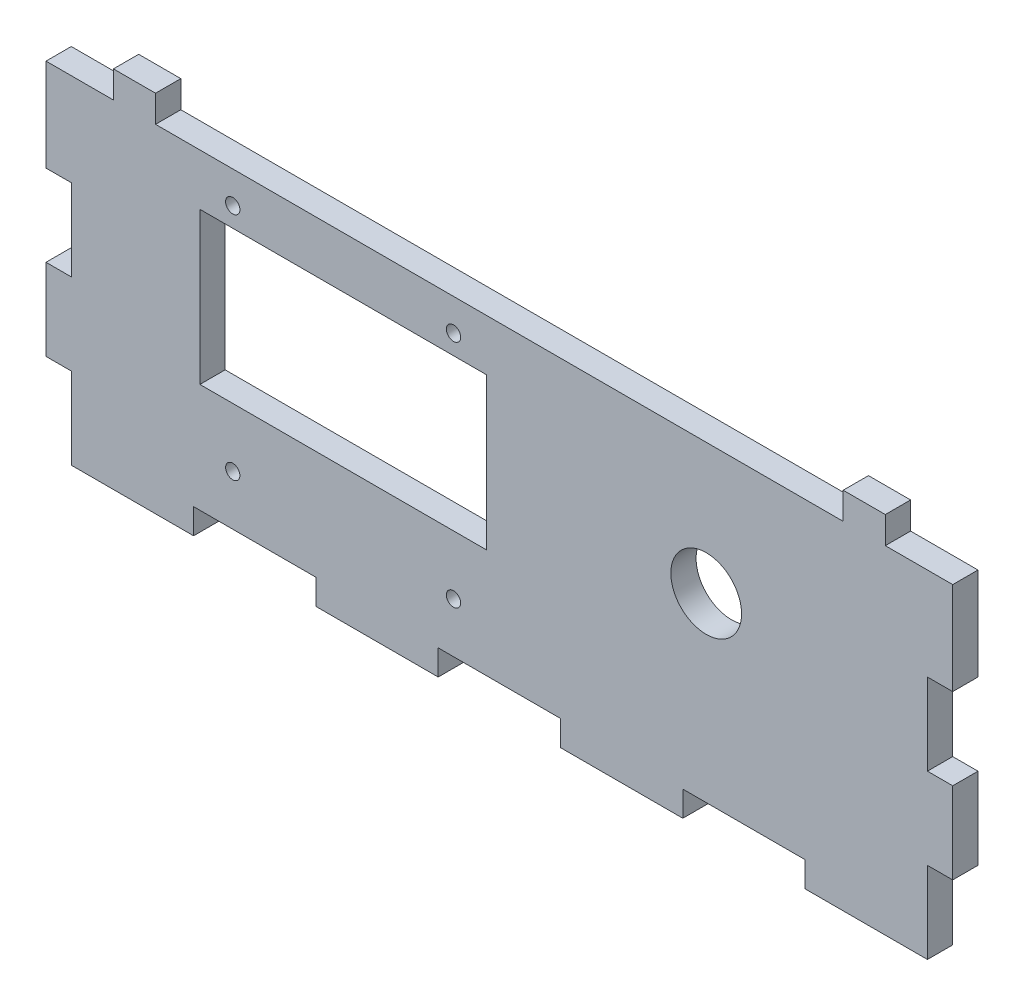
SolidWorks part; units mm, degrees
ref_plane "Alzado" through (0, 0, 0) normal (0, 0, 1) x (1, 0, 0)
ref_plane "Planta" through (0, 0, 0) normal (0, 1, 0) x (1, 0, 0)
ref_plane "Vista lateral" through (0, 0, 0) normal (1, 0, 0) x (0, 0, -1)
sketch "Croquis1" plane through (0, 0, 0) normal (0, 0, 1) x (1, 0, 0)
  line L0 (0, -17.0016) -> (0, -14.0016)
  line L1 (-48.39, -14.0016) -> (0, -14.0016) construction
  line L2 (0, -17.0016) -> (104.61, -17.0016)
  line L3 (101.61, -17.0016) -> (101.61, -49.332) construction
  line L4 (-227.956, -78.0016) -> (93.758, -78.0016) construction
  line L5 (-48.39, -14.0016) -> (-48.39, -78.0016) construction
  line L6 (78.6222, -39.0016) -> (-38.712, -39.0016) construction
  line L7 (0, -14.0016) -> (0, -17.0016) construction
  line L8 (0, -17.0016) -> (-48.39, -17.0016) construction
  line L9 (-48.39, -14.0016) -> (-38.712, -14.0016)
  line L10 (-38.712, -14.0016) -> (-38.712, -17.0016)
  line L11 (-38.712, -17.0016) -> (-29.034, -17.0016)
  line L12 (-29.034, -17.0016) -> (-29.034, -14.0016)
  line L13 (-29.034, -14.0016) -> (-19.356, -14.0016)
  line L14 (-19.356, -14.0016) -> (-19.356, -17.0016)
  line L15 (-19.356, -17.0016) -> (-9.678, -17.0016)
  line L16 (-9.678, -17.0016) -> (-9.678, -14.0016)
  line L17 (-9.678, -14.0016) -> (0, -14.0016)
  line L18 (104.61, -17.0016) -> (104.61, -78.0016) construction
  line L19 (104.61, -17.0016) -> (104.61, -29.2016)
  line L20 (104.61, -29.2016) -> (101.61, -29.2016)
  line L21 (101.61, -29.2016) -> (101.61, -41.4016)
  line L22 (101.61, -41.4016) -> (104.61, -41.4016)
  line L23 (104.61, -41.4016) -> (104.61, -53.6016)
  line L24 (104.61, -53.6016) -> (101.61, -53.6016)
  line L25 (101.61, -53.6016) -> (101.61, -65.8016)
  line L26 (101.61, -65.8016) -> (104.61, -65.8016)
  line L27 (104.61, -65.8016) -> (104.61, -78.0016)
  line L28 (-45.39, -56.5563) -> (-45.39, 45.6638) construction
  line L29 (-48.39, -14.0016) -> (-48.39, -26.8016)
  line L30 (-48.39, -26.8016) -> (-45.39, -26.8016)
  line L31 (-45.39, -26.8016) -> (-45.39, -39.6016)
  line L32 (-45.39, -39.6016) -> (-48.39, -39.6016)
  line L33 (-48.39, -39.6016) -> (-48.39, -52.4016)
  line L34 (-48.39, -52.4016) -> (-45.39, -52.4016)
  line L35 (-45.39, -52.4016) -> (-45.39, -65.2016)
  line L36 (-45.39, -65.2016) -> (-48.39, -65.2016)
  line L37 (-48.39, -65.2016) -> (-48.39, -78.0016)
  line L38 (-102.5031, -75.0016) -> (75.9308, -75.0016) construction
  line L39 (-124.386, -156.1001) -> (179.1879, -156.1001) construction
  line L40 (-48.39, -153.1001) -> (104.61, -153.1001) construction
  line L41 (-48.39, -78.0016) -> (-34.4809, -78.0016)
  line L42 (-34.4809, -78.0016) -> (-34.4809, -75.0016)
  line L43 (-34.4809, -75.0016) -> (-20.5718, -75.0016)
  line L44 (-20.5718, -75.0016) -> (-20.5718, -78.0016)
  line L45 (-20.5718, -78.0016) -> (-6.6627, -78.0016)
  line L46 (-6.6627, -78.0016) -> (-6.6627, -75.0016)
  line L47 (-6.6627, -75.0016) -> (7.2464, -75.0016)
  line L48 (7.2464, -75.0016) -> (7.2464, -78.0016)
  line L49 (7.2464, -78.0016) -> (21.1555, -78.0016)
  line L50 (21.1555, -78.0016) -> (21.1555, -75.0016)
  line L51 (21.1555, -75.0016) -> (35.0645, -75.0016)
  line L52 (35.0645, -75.0016) -> (35.0645, -78.0016)
  line L53 (35.0645, -78.0016) -> (48.9736, -78.0016)
  line L54 (48.9736, -78.0016) -> (48.9736, -75.0016)
  line L55 (48.9736, -75.0016) -> (62.8827, -75.0016)
  line L56 (62.8827, -75.0016) -> (62.8827, -78.0016)
  line L57 (62.8827, -78.0016) -> (76.7918, -78.0016)
  line L58 (76.7918, -78.0016) -> (76.7918, -75.0016)
  line L59 (76.7918, -75.0016) -> (90.7009, -75.0016)
  line L60 (90.7009, -75.0016) -> (90.7009, -78.0016)
  line L61 (90.7009, -78.0016) -> (104.61, -78.0016)
  line L62 (-48.39, -153.1001) -> (-48.39, -260.7101) construction
  line L63 (-48.39, -260.7101) -> (104.61, -260.7101) construction
  line L64 (104.61, -153.1001) -> (104.61, -260.7101) construction
  line L65 (-68.7634, -257.7101) -> (144.8732, -257.7101) construction
  line L66 (101.61, -78.0016) -> (101.61, -269.1968) construction
  line L67 (-45.39, -153.1001) -> (-45.39, -251.8965) construction
  line L68 (-34.4809, -78.0016) -> (-34.4809, -243.0877) construction
  line L69 (-20.5718, -78.0016) -> (-20.5718, -243.0877) construction
  line L70 (-6.6627, -75.0016) -> (-6.6627, -243.0877) construction
  line L71 (7.2464, -75.0016) -> (7.2464, -243.0877) construction
  line L72 (21.1555, -75.0016) -> (21.1555, -243.0877) construction
  line L73 (35.0645, -75.0016) -> (35.0645, -243.0877) construction
  line L74 (48.9736, -75.0016) -> (48.9736, -243.0877) construction
  line L75 (62.8827, -75.0016) -> (62.8827, -243.0877) construction
  line L76 (76.7918, -75.0016) -> (76.7918, -243.0877) construction
  line L77 (90.7009, -75.0016) -> (90.7009, -243.0877) construction
  line L78 (-34.4809, -156.1001) -> (-48.39, -156.1001)
  line L79 (-34.4809, -156.1001) -> (-34.4809, -153.1001)
  line L80 (-34.4809, -153.1001) -> (-20.5718, -153.1001)
  line L81 (-20.5718, -153.1001) -> (-20.5718, -156.1001)
  line L82 (-20.5718, -156.1001) -> (-6.6627, -156.1001)
  line L83 (-6.6627, -156.1001) -> (-6.6627, -153.1001)
  line L84 (-6.6627, -153.1001) -> (7.2464, -153.1001)
  line L85 (7.2464, -153.1001) -> (7.2464, -156.1001)
  line L86 (7.2464, -156.1001) -> (21.1555, -156.1001)
  line L87 (21.1555, -156.1001) -> (21.1555, -153.1001)
  line L88 (21.1555, -153.1001) -> (35.0645, -153.1001)
  line L89 (35.0645, -153.1001) -> (35.0645, -156.1001)
  line L90 (35.0645, -156.1001) -> (48.9736, -156.1001)
  line L91 (48.9736, -156.1001) -> (48.9736, -153.1001)
  line L92 (48.9736, -153.1001) -> (62.8827, -153.1001)
  line L93 (62.8827, -153.1001) -> (62.8827, -156.1001)
  line L94 (62.8827, -156.1001) -> (76.7918, -156.1001)
  line L95 (76.7918, -156.1001) -> (76.7918, -153.1001)
  line L96 (76.7918, -153.1001) -> (90.7009, -153.1001)
  line L97 (90.7009, -153.1001) -> (90.7009, -156.1001)
  line L98 (90.7009, -156.1001) -> (104.61, -156.1001)
  line L99 (-48.39, -257.7101) -> (-34.4809, -257.7101)
  line L100 (-34.4809, -257.7101) -> (-34.4809, -260.7101)
  line L101 (-34.4809, -260.7101) -> (-20.5718, -260.7101)
  line L102 (-20.5718, -260.7101) -> (-20.5718, -257.7101)
  line L103 (-20.5718, -257.7101) -> (-6.6627, -257.7101)
  line L104 (-6.6627, -257.7101) -> (-6.6627, -260.7101)
  line L105 (-6.6627, -260.7101) -> (7.2464, -260.7101)
  line L106 (7.2464, -260.7101) -> (7.2464, -257.7101)
  line L107 (7.2464, -257.7101) -> (21.1555, -257.7101)
  line L108 (21.1555, -257.7101) -> (21.1555, -260.7101)
  line L109 (21.1555, -260.7101) -> (35.0645, -260.7101)
  line L110 (35.0645, -260.7101) -> (35.0645, -257.7101)
  line L111 (35.0645, -257.7101) -> (48.9736, -257.7101)
  line L112 (48.9736, -257.7101) -> (48.9736, -260.7101)
  line L113 (48.9736, -260.7101) -> (62.8827, -260.7101)
  line L114 (62.8827, -260.7101) -> (62.8827, -257.7101)
  line L115 (62.8827, -257.7101) -> (76.7918, -257.7101)
  line L116 (76.7918, -257.7101) -> (76.7918, -260.7101)
  line L117 (76.7918, -260.7101) -> (90.7009, -260.7101)
  line L118 (90.7009, -260.7101) -> (90.7009, -257.7101)
  line L119 (90.7009, -257.7101) -> (104.61, -257.7101)
  line L120 (-226.2526, -14.0016) -> (-226.2526, -78.0016) construction
  line L121 (-290.2526, -78.0016) -> (-226.2526, -78.0016) construction
  line L122 (-226.2526, -78.0016) -> (-226.2526, -287.7111) construction
  line L123 (-290.2526, -78.0016) -> (-290.2526, -287.7111) construction
  line L124 (-290.2526, -287.7111) -> (-226.2526, -287.7111) construction
  line L125 (-48.39, -26.8016) -> (-105.5506, -26.8016) construction
  line L126 (-48.39, -39.6016) -> (-94.7516, -39.6016) construction
  line L127 (-48.39, -52.4016) -> (-71.8061, -52.4016) construction
  line L128 (-48.39, -65.2016) -> (-67.7461, -65.2016) construction
  line L129 (-277.4526, -73.8444) -> (-277.4526, -111.8004) construction
  line L130 (-264.6526, -73.8444) -> (-264.6526, -111.8004) construction
  line L131 (-251.8526, -90.832) -> (-251.8526, -128.788) construction
  line L132 (-239.0526, -73.8444) -> (-239.0526, -111.8004) construction
  line L133 (-229.2526, -73.8444) -> (-229.2526, -93.389) construction
  line L134 (165.3571, -156.1001) -> (174.5571, -156.1001)
  line L135 (174.5571, -156.1001) -> (174.5571, -153.1001)
  line L136 (174.5571, -153.1001) -> (186.7571, -153.1001)
  line L137 (186.7571, -153.1001) -> (186.7571, -156.1001)
  line L138 (186.7571, -156.1001) -> (198.9571, -156.1001)
  line L139 (198.9571, -156.1001) -> (198.9571, -153.1001)
  line L140 (198.9571, -153.1001) -> (211.1571, -153.1001)
  line L141 (211.1571, -153.1001) -> (211.1571, -156.1001)
  line L142 (211.1571, -156.1001) -> (223.3571, -156.1001)
  line L143 (-229.2526, -156.1001) -> (-229.2526, -170.6158)
  line L144 (-229.2526, -170.6158) -> (-226.2526, -170.6158)
  line L145 (-226.2526, -170.6158) -> (-226.2526, -185.1315)
  line L146 (-226.2526, -185.1315) -> (-229.2526, -185.1315)
  line L147 (-229.2526, -185.1315) -> (-229.2526, -199.6473)
  line L148 (-229.2526, -199.6473) -> (-226.2526, -199.6473)
  line L149 (-226.2526, -199.6473) -> (-226.2526, -220.163)
  line L150 (-226.2526, -220.163) -> (-229.2526, -220.163)
  line L151 (-48.39, -257.7101) -> (-48.39, -243.1944)
  line L152 (-48.39, -243.1944) -> (-45.39, -243.1944)
  line L153 (-45.39, -243.1944) -> (-45.39, -228.6787)
  line L154 (-45.39, -228.6787) -> (-48.39, -228.6787)
  line L155 (-48.39, -228.6787) -> (-48.39, -214.163)
  line L156 (-48.39, -214.163) -> (-45.39, -214.163)
  line L157 (-45.39, -214.163) -> (-45.39, -199.6473)
  line L158 (-45.39, -199.6473) -> (-48.39, -199.6473)
  line L159 (-48.39, -199.6473) -> (-48.39, -185.1315)
  line L160 (-48.39, -185.1315) -> (-45.39, -185.1315)
  line L161 (-45.39, -185.1315) -> (-45.39, -170.6158)
  line L162 (-45.39, -170.6158) -> (-48.39, -170.6158)
  line L163 (-48.39, -170.6158) -> (-48.39, -156.1001)
  line L164 (-48.39, -228.6787) -> (-80.3979, -228.6787) construction
  line L165 (-48.39, -243.1944) -> (-76.899, -243.1944) construction
  line L166 (-48.39, -214.163) -> (-74.7996, -214.163) construction
  line L167 (-48.39, -199.6473) -> (-74.7996, -199.6473) construction
  line L168 (-74.7996, -185.1315) -> (-48.39, -185.1315) construction
  line L169 (-48.39, -170.6158) -> (-71.0675, -170.6158) construction
  line L170 (-229.2526, -220.163) -> (-229.2526, -234.6787)
  line L171 (-287.2526, -73.8444) -> (-287.2526, -109.848) construction
  line L172 (-229.2526, -234.6787) -> (-226.2526, -234.6787)
  line L173 (-226.2526, -234.6787) -> (-226.2526, -249.1944)
  line L174 (-226.2526, -249.1944) -> (-229.2526, -249.1944)
  line L175 (-229.2526, -249.1944) -> (-229.2526, -257.7101)
  line L176 (223.3571, -257.7101) -> (211.1571, -257.7101)
  line L177 (211.1571, -257.7101) -> (211.1571, -260.7101)
  line L178 (211.1571, -260.7101) -> (198.9571, -260.7101)
  line L179 (198.9571, -260.7101) -> (198.9571, -257.7101)
  line L180 (198.9571, -257.7101) -> (186.7571, -257.7101)
  line L181 (186.7571, -257.7101) -> (186.7571, -260.7101)
  line L182 (186.7571, -260.7101) -> (174.5571, -260.7101)
  line L183 (174.5571, -260.7101) -> (174.5571, -257.7101)
  line L184 (-287.2526, -257.7101) -> (-287.2526, -243.1944)
  line L185 (-287.2526, -243.1944) -> (-290.2526, -243.1944)
  line L186 (-290.2526, -243.1944) -> (-290.2526, -228.6787)
  line L187 (-290.2526, -228.6787) -> (-287.2526, -228.6787)
  line L188 (-287.2526, -228.6787) -> (-287.2526, -214.163)
  line L189 (-287.2526, -214.163) -> (-290.2526, -214.163)
  line L190 (-290.2526, -214.163) -> (-290.2526, -199.6473)
  line L191 (-290.2526, -199.6473) -> (-287.2526, -199.6473)
  line L192 (-287.2526, -199.6473) -> (-287.2526, -185.1315)
  line L193 (-287.2526, -185.1315) -> (-290.2526, -185.1315)
  line L194 (-290.2526, -185.1315) -> (-290.2526, -170.6158)
  line L195 (-290.2526, -170.6158) -> (-287.2526, -170.6158)
  line L196 (-287.2526, -170.6158) -> (-287.2526, -156.1001)
  line L197 (174.5571, -257.7101) -> (165.3571, -257.7101)
  line L198 (-315.487, -120.5373) -> (-315.487, -274.6014) construction
  line L199 (-423.097, -153.1001) -> (-423.097, -80.2802) construction
  line L200 (-420.097, -153.1001) -> (-420.097, -73.0846) construction
  line L201 (-405.5813, -153.1001) -> (-405.5813, -73.0846) construction
  line L202 (-391.0655, -153.1001) -> (-391.0655, -77.6291) construction
  line L203 (-376.5498, -153.1001) -> (-376.5498, -80.2802) construction
  line L204 (-362.0341, -153.1001) -> (-362.0341, -73.0846) construction
  line L205 (-347.5184, -153.1001) -> (-347.5184, -77.6291) construction
  line L206 (-333.0027, -153.1001) -> (-333.0027, -73.0846) construction
  line L207 (-318.487, -153.1001) -> (-318.487, -77.6291) construction
  line L208 (-48.39, -21.6772) -> (-48.39, 38.9813) construction
  line L209 (-38.712, -14.0016) -> (-38.712, 45.6638) construction
  line L210 (-29.034, -14.0016) -> (-29.034, 45.6638) construction
  line L211 (-19.356, -14.0016) -> (-19.356, 45.6638) construction
  line L212 (-9.678, -14.0016) -> (-9.678, 45.6638) construction
  line L213 (0, -14.0016) -> (0, 45.6638) construction
  line L214 (2.5149, 38.1832) -> (-48.39, 38.1832) construction
  line L215 (-48.39, 86.5732) -> (-80.1148, 86.5732) construction
  line L216 (-48.39, 76.8952) -> (-75.2531, 76.8952) construction
  line L217 (-48.39, 67.2172) -> (-75.2531, 67.2172) construction
  line L218 (-48.39, 57.5392) -> (-80.1148, 57.5392) construction
  line L219 (-48.39, 47.8612) -> (-84.9766, 47.8612) construction
  line L220 (-318.487, 38.1832) -> (-318.487, 47.8612)
  line L221 (-48.39, 38.1832) -> (-76.9441, 38.1832) construction
  line L222 (-318.487, 47.8612) -> (-315.487, 47.8612)
  line L223 (-315.487, 47.8612) -> (-315.487, 57.5392)
  line L224 (-315.487, 57.5392) -> (-318.487, 57.5392)
  line L225 (-318.487, 57.5392) -> (-318.487, 67.2172)
  line L226 (-420.097, 78.2172) -> (-415.097, 78.2172)
  line L227 (-415.097, 78.2172) -> (-415.097, 81.4172)
  line L228 (-415.097, 81.4172) -> (-410.097, 81.4172)
  line L229 (-318.487, 67.2172) -> (-315.487, 67.2172)
  line L230 (-315.487, 67.2172) -> (-315.487, 78.2172)
  line L231 (-315.487, 78.2172) -> (-318.487, 78.2172)
  line L232 (-420.097, 67.2172) -> (-423.097, 67.2172)
  line L233 (-423.097, 67.2172) -> (-423.097, 78.2172)
  line L234 (-423.097, 78.2172) -> (-420.097, 78.2172)
  line L235 (-420.097, 67.2172) -> (-420.097, 57.5392)
  line L236 (-420.097, 57.5392) -> (-423.097, 57.5392)
  line L237 (-423.097, 57.5392) -> (-423.097, 47.8612)
  line L238 (-423.097, 47.8612) -> (-420.097, 47.8612)
  line L239 (-420.097, 47.8612) -> (-420.097, 38.1832)
  line L240 (-48.39, 41.1832) -> (-83.9517, 41.1832) construction
  line L241 (-318.487, 38.1832) -> (-333.0027, 38.1832)
  line L242 (-333.0027, 38.1832) -> (-333.0027, 41.1832)
  line L243 (-333.0027, 41.1832) -> (-347.5184, 41.1832)
  line L244 (-347.5184, 41.1832) -> (-347.5184, 38.1832)
  line L245 (-347.5184, 38.1832) -> (-362.0341, 38.1832)
  line L246 (-362.0341, 38.1832) -> (-362.0341, 41.1832)
  line L247 (-362.0341, 41.1832) -> (-376.5498, 41.1832)
  line L248 (-376.5498, 41.1832) -> (-376.5498, 38.1832)
  line L249 (-376.5498, 38.1832) -> (-391.0655, 38.1832)
  line L250 (-391.0655, 38.1832) -> (-391.0655, 41.1832)
  line L251 (-391.0655, 41.1832) -> (-405.5813, 41.1832)
  line L252 (-405.5813, 41.1832) -> (-405.5813, 38.1832)
  line L253 (-405.5813, 38.1832) -> (-420.097, 38.1832)
  line L254 (162.3571, -15.1529) -> (162.3571, -104.9762) construction
  line L255 (104.61, -29.2016) -> (145.8916, -29.2016) construction
  line L256 (104.61, -41.4016) -> (145.8916, -41.4016) construction
  line L257 (104.61, -65.8016) -> (131.4417, -65.8016) construction
  line L258 (104.61, -53.6016) -> (126.5441, -53.6016) construction
  line L259 (165.3571, -73.8444) -> (165.3571, -106.8492) construction
  line L260 (174.5571, -73.8444) -> (174.5571, -108.8044) construction
  line L261 (186.7571, -73.8444) -> (186.7571, -108.8044) construction
  line L262 (198.9571, -73.8444) -> (198.9571, -108.8044) construction
  line L263 (211.1571, -73.8444) -> (211.1571, -106.8492) construction
  line L264 (223.3571, -73.8444) -> (223.3571, -108.8044) construction
  line L265 (104.61, -257.7101) -> (104.61, -243.0877)
  line L266 (104.61, -243.0877) -> (101.61, -243.0877)
  line L267 (101.61, -243.0877) -> (101.61, -228.6787)
  line L268 (101.61, -228.6787) -> (104.61, -228.6787)
  line L269 (104.61, -228.6787) -> (104.61, -214.163)
  line L270 (104.61, -214.163) -> (101.61, -214.163)
  line L271 (101.61, -214.163) -> (101.61, -199.6473)
  line L272 (101.61, -199.6473) -> (104.61, -199.6473)
  line L273 (104.61, -199.6473) -> (104.61, -185.1315)
  line L274 (104.61, -185.1315) -> (101.61, -185.1315)
  line L275 (101.61, -185.1315) -> (101.61, -170.6158)
  line L276 (101.61, -170.6158) -> (104.61, -170.6158)
  line L277 (104.61, -170.6158) -> (104.61, -156.1001)
  line L278 (-229.2526, -156.1001) -> (-239.0526, -156.1001)
  line L279 (-239.0526, -156.1001) -> (-239.0526, -153.1001)
  line L280 (-239.0526, -153.1001) -> (-251.8526, -153.1001)
  line L281 (-251.8526, -153.1001) -> (-251.8526, -156.1001)
  line L282 (-251.8526, -156.1001) -> (-264.6526, -156.1001)
  line L283 (-264.6526, -156.1001) -> (-264.6526, -153.1001)
  line L284 (-264.6526, -153.1001) -> (-277.4526, -153.1001)
  line L285 (-277.4526, -153.1001) -> (-277.4526, -156.1001)
  line L286 (-277.4526, -156.1001) -> (-287.2526, -156.1001)
  line L287 (223.3571, -156.1001) -> (223.3571, -257.7101)
  line L288 (-229.2526, -257.7101) -> (-239.0526, -257.7101)
  line L289 (-239.0526, -257.7101) -> (-239.0526, -260.7101)
  line L290 (-239.0526, -260.7101) -> (-251.8526, -260.7101)
  line L291 (-251.8526, -260.7101) -> (-251.8526, -257.7101)
  line L292 (-251.8526, -257.7101) -> (-264.6526, -257.7101)
  line L293 (-264.6526, -257.7101) -> (-264.6526, -260.7101)
  line L294 (-264.6526, -260.7101) -> (-277.4526, -260.7101)
  line L295 (-277.4526, -260.7101) -> (-277.4526, -257.7101)
  line L296 (-277.4526, -257.7101) -> (-287.2526, -257.7101)
  line L297 (165.3571, -257.7101) -> (165.3571, -243.1944)
  line L298 (165.3571, -243.1944) -> (162.3571, -243.1944)
  line L299 (162.3571, -243.1944) -> (162.3571, -228.6787)
  line L300 (162.3571, -228.6787) -> (165.3571, -228.6787)
  line L301 (165.3571, -228.6787) -> (165.3571, -214.163)
  line L302 (165.3571, -214.163) -> (162.3571, -214.163)
  line L303 (162.3571, -214.163) -> (162.3571, -199.6473)
  line L304 (162.3571, -199.6473) -> (165.3571, -199.6473)
  line L305 (165.3571, -199.6473) -> (165.3571, -185.1315)
  line L306 (165.3571, -185.1315) -> (162.3571, -185.1315)
  line L307 (162.3571, -185.1315) -> (162.3571, -170.6158)
  line L308 (162.3571, -170.6158) -> (165.3571, -170.6158)
  line L309 (165.3571, -170.6158) -> (165.3571, -156.1001)
  line L310 (-410.097, 81.4172) -> (-410.097, 78.2172)
  line L311 (-410.097, 78.2172) -> (-328.487, 78.2172)
  line L312 (-328.487, 78.2172) -> (-328.487, 81.4172)
  line L313 (-328.487, 81.4172) -> (-323.487, 81.4172)
  line L314 (-323.487, 81.4172) -> (-323.487, 78.2172)
  line L315 (-323.487, 78.2172) -> (-318.487, 78.2172)
  line L316 (-387.8334, 82.1992) -> (-387.8334, 35.672) construction
  line L317 (-404.8334, 72.1162) -> (-370.8334, 72.1162)
  line L318 (-404.8334, 72.1162) -> (-404.8334, 54.1162)
  line L319 (-404.8334, 54.1162) -> (-370.8334, 54.1162)
  line L320 (-370.8334, 72.1162) -> (-370.8334, 54.1162)
  circle A0 centre (73.11, -39.0016) radius 1.25
  circle A1 centre (31.5, -39.0016) radius 1.25
  circle A2 centre (-28.49, -39.0016) radius 1.25
  arc A3 (-226.2526, -65.2016) -> (-239.0526, -78.0016) centre (-226.2526, -78.0016) ccw construction
  arc A4 (-226.2526, -52.4016) -> (-251.8526, -78.0016) centre (-226.2526, -78.0016) ccw construction
  arc A5 (-226.2526, -39.6016) -> (-264.6526, -78.0016) centre (-226.2526, -78.0016) ccw construction
  arc A6 (-226.2526, -26.8016) -> (-277.4526, -78.0016) centre (-226.2526, -78.0016) ccw construction
  arc A7 (-226.2526, -14.0016) -> (-290.2526, -78.0016) centre (-226.2526, -78.0016) ccw construction
  arc A8 (-226.2526, -75.0016) -> (-229.2526, -78.0016) centre (-226.2526, -78.0016) ccw construction
  arc A9 (-226.2526, -17.0016) -> (-287.2526, -78.0016) centre (-226.2526, -78.0016) ccw construction
  arc A10 (-315.487, -156.1001) -> (-318.487, -153.1001) centre (-315.487, -153.1001) cw construction
  arc A11 (-315.487, -170.6158) -> (-333.0027, -153.1001) centre (-315.487, -153.1001) cw construction
  arc A12 (-315.487, -185.1315) -> (-347.5184, -153.1001) centre (-315.487, -153.1001) cw construction
  arc A13 (-315.487, -199.6473) -> (-362.0341, -153.1001) centre (-315.487, -153.1001) cw construction
  arc A14 (-315.487, -214.163) -> (-376.5498, -153.1001) centre (-315.487, -153.1001) cw construction
  arc A15 (-315.487, -228.6787) -> (-391.0655, -153.1001) centre (-315.487, -153.1001) cw construction
  arc A16 (-315.487, -243.1944) -> (-405.5813, -153.1001) centre (-315.487, -153.1001) cw construction
  arc A17 (-315.487, -257.7101) -> (-420.097, -153.1001) centre (-315.487, -153.1001) cw construction
  arc A18 (-315.487, -260.7101) -> (-423.097, -153.1001) centre (-315.487, -153.1001) cw construction
  arc A19 (-45.39, 38.1832) -> (-48.39, 41.1832) centre (-48.39, 38.1832) ccw construction
  arc A20 (-38.712, 38.1832) -> (-48.39, 47.8612) centre (-48.39, 38.1832) ccw construction
  arc A21 (-29.034, 38.1832) -> (-48.39, 57.5392) centre (-48.39, 38.1832) ccw construction
  arc A22 (-19.356, 38.1832) -> (-48.39, 67.2172) centre (-48.39, 38.1832) ccw construction
  arc A23 (-9.678, 38.1832) -> (-48.39, 76.8952) centre (-48.39, 38.1832) ccw construction
  arc A24 (0, 38.1832) -> (-48.39, 86.5732) centre (-48.39, 38.1832) ccw construction
  arc A25 (162.3571, -75.0016) -> (165.3571, -78.0016) centre (162.3571, -78.0016) cw construction
  arc A26 (162.3571, -65.8016) -> (174.5571, -78.0016) centre (162.3571, -78.0016) cw construction
  arc A27 (162.3571, -53.6016) -> (186.7571, -78.0016) centre (162.3571, -78.0016) cw construction
  arc A28 (162.3571, -41.4016) -> (198.9571, -78.0016) centre (162.3571, -78.0016) cw construction
  arc A29 (162.3571, -29.2016) -> (211.1571, -78.0016) centre (162.3571, -78.0016) cw construction
  arc A30 (162.3571, -17.0016) -> (223.3571, -78.0016) centre (162.3571, -78.0016) cw construction
  circle A31 centre (-374.7334, 74.4362) radius 0.85
  circle A32 centre (-400.9334, 74.4362) radius 0.85
  circle A33 centre (-400.9334, 47.1162) radius 0.85
  circle A34 centre (-374.7334, 47.1162) radius 0.85
  circle A35 centre (-344.744, 62.6718) radius 4.2
  text T0 "TOP\r\n"
  dimension "D2" = 2.5
  dimension "D3" = 2.5
  dimension "D4" = 2.5
  dimension "D7" = 101.6
  dimension "D20" = 22
  dimension "D9" = 36
  dimension "D26" = 1.7
  dimension "D29" = 1.7
  dimension "D24" = 1.7
  dimension "D28" = 1.7
  dimension "D33" = 8.4
  dimension "D1" = 153
  dimension "D5" = 3
  dimension "D6" = 104.61
  dimension "D8" = 3
  dimension "D10" = 3
  dimension "D11" = 41.61
  dimension "D12" = 5
  dimension "D13" = 3
  dimension "D14" = 153
  dimension "D15" = 107.61
  dimension "D16" = 5
  dimension "D17" = 3
  dimension "D18" = 3
  dimension "D19" = 28.5
  dimension "D21" = 5
  dimension "D22" = 5
  dimension "D23" = 3.2
  dimension "D25" = 34
  dimension "D27" = 26.2
  dimension "D30" = 7
  dimension "D31" = 27.32
  dimension "D32" = 18
extrude "Saliente-Extruir1" add sketch "Croquis1" along normal blind 3 contours L253 L252 L251 L250 L249 L248 L247 L246 L245 L244 L243 L242 L241 L220 L222 L223 L224 L225 L235 L236 L237 L238 L239 region at (-366.3198, 58.3376, 0)
